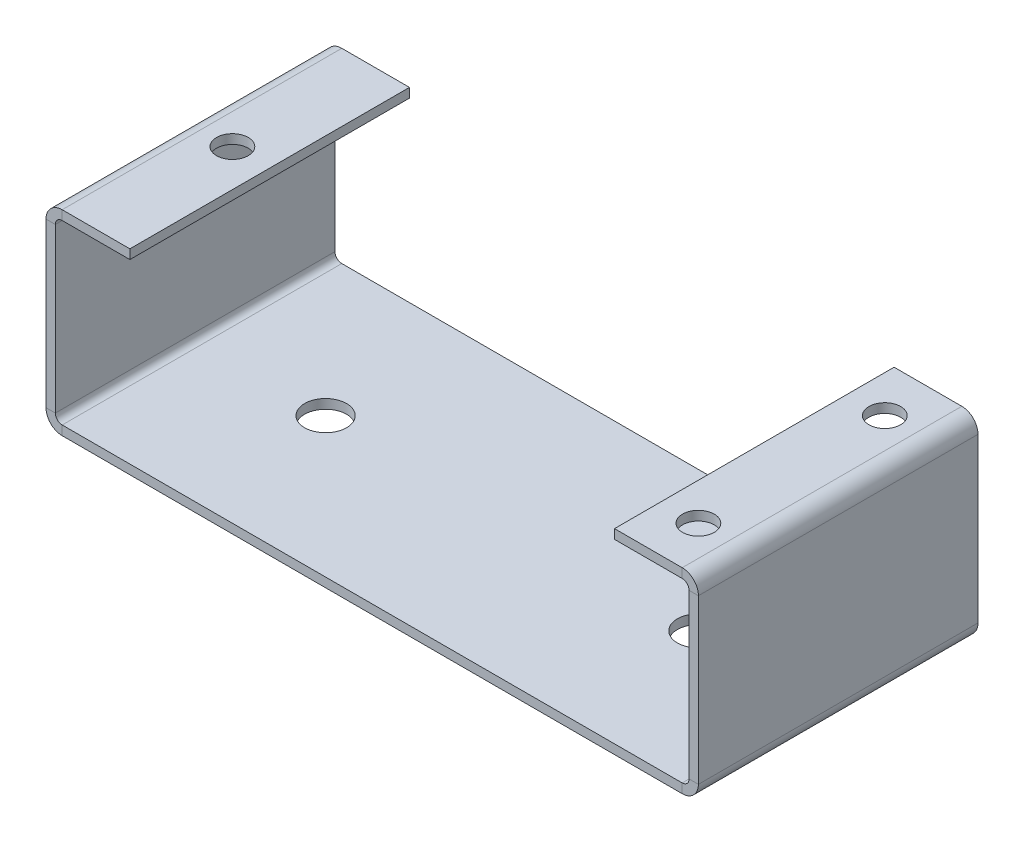
SolidWorks part; units mm, degrees
note: The reader was unsure of these and kept them because the rebuilt part matched: flange length of "Tôle pliée sur arête1", "Tôle pliée sur arête2".
ref_plane "Plan de face" through (0, 0, 0) normal (0, 0, 1) x (1, 0, 0)
ref_plane "Plan de dessus" through (0, 0, 0) normal (0, 1, 0) x (1, 0, 0)
ref_plane "Plan de droite" through (0, 0, 0) normal (1, 0, 0) x (0, 0, -1)
sketch "Esquisse1" plane through (0, 0, 0) normal (0, 1, 0) x (1, 0, 0)
  line L1 (-35, -15) -> (35, -15)
  line L2 (-35, -15) -> (-35, 15)
  line L3 (-35, 15) -> (35, 15)
  line L4 (35, -15) -> (35, 15)
  line L5 (-35, -15) -> (35, 15) construction
  line L6 (-35, 15) -> (35, -15) construction
  line L9 (-11.55, 0) -> (11.55, 0) construction
  point P0 (0, 0)
  dimension "D1" = 30
  dimension "D2" = 70
base flange "Tôle de base pliée1" sketch "Esquisse1" thickness 1 reverse thickness direction yes parameters "D1"=0.7366
edge flange "Tôle pliée sur arête1" sketch "Esquisse8" flange profiles "Esquisse8", "Esquisse36" flange angle 90 flange length 20 flange position material inside bend radius 0.7366 thickness 1 relief rectangular parameters "D6"=10, "D8"=1
sketch "Esquisse8" plane through (-35, 1, 0) normal (-1, 0, 0) x (0, 0, 1)
  line L0 (-15, 0) -> (15, 0) construction
  line L1 (-15, 0) -> (15, 0)
  line L2 (-15, 0) -> (-15, 20)
  line L3 (-15, 20) -> (15, 20)
  line L4 (15, 20) -> (15, 0)
sketch "Esquisse36" plane through (35, 1, 0) normal (1, 0, 0) x (0, 0, -1)
  line L0 (-15, 0) -> (15, 0) construction
  line L1 (-15, 0) -> (15, 0)
  line L2 (-15, 0) -> (-15, 20)
  line L3 (-15, 20) -> (15, 20)
  line L4 (15, 20) -> (15, 0)
bend "Pli d'arête1" bend radius 0.7366 bend angle 90 parameters "D5"=1
bend "Pli d'arête5" bend radius 0.7366 bend angle 90 parameters "D5"=3
edge flange "Tôle pliée sur arête2" sketch "Esquisse11" flange profiles "Esquisse11", "Esquisse38" flange angle 90 flange length 9 flange position material inside bend radius 0.7366 thickness 1 relief rectangular parameters "D6"=10, "D8"=1
sketch "Esquisse11" plane through (-34, 21, 0) normal (0, 1, 0) x (0, 0, 1)
  line L0 (15, 0) -> (-15, 0) construction
  line L1 (15, 0) -> (-15, 0)
  line L2 (-15, 0) -> (-15, 8)
  line L3 (-15, 8) -> (15, 8)
  line L4 (15, 8) -> (15, 0)
sketch "Esquisse38" plane through (34, 21, 0) normal (0, 1, 0) x (0, 0, -1)
  line L0 (15, 0) -> (-15, 0) construction
  line L1 (15, 0) -> (-15, 0)
  line L2 (-15, 0) -> (-15, 8)
  line L3 (-15, 8) -> (15, 8)
  line L4 (15, 8) -> (15, 0)
bend "Pli d'arête2" bend radius 0.7366 bend angle 90 parameters "D5"=2
bend "Pli d'arête6" bend radius 0.7366 bend angle 90 parameters "D5"=5
sketch "Esquisse12" plane through (0, 21, 0) normal (0, 1, 0) x (1, 0, 0)
  line L0 (-11.55, 0) -> (11.55, 0) construction
  line L2 (35, 15) -> (35, -15) construction
  line L3 (33.2634, 15) -> (26, 15) construction
  line L7 (-35, -15) -> (-35, 15) construction
  circle A2 centre (-30, 0) radius 1.7
  circle A3 centre (30, 10) radius 1.7
  circle A4 centre (30, -10) radius 1.7
  dimension "D2" = 5
  dimension "D3" = 3.4
  dimension "D1" = 3.4
  dimension "D4" = 5
  dimension "D5" = 5
extrude "Enlèv. mat.-Extru.1" cut sketch "Esquisse12" against normal up to next normal cut yes
sketch "Esquisse27" plane through (0, 1, 0) normal (0, 1, 0) x (1, 0, 0)
  line L0 (-11.55, 0) -> (11.55, 0) construction
  line L1 (0, -11.55) -> (0, 11.55) construction
  circle A0 centre (-20, 0) radius 2.25
  circle A1 centre (20, 0) radius 2.25
  dimension "D1" = 4.5
  dimension "D2" = 20
extrude "Enlèv. mat.-Extru.3" cut sketch "Esquisse27" against normal up to next normal cut yes
sketch "Lignes de pliage1" [suppressed] plane through (0, 0, 0) normal (0, 1, 0) x (1, 0, 0)
sketch "Cube de visualisation1" [suppressed] plane through (0, 0, 0) normal (0, 1, 0) x (1, 0, 0)
sheet metal parameters "Tôlerie1" thickness 1 parameters "D1"=0.7366
flat pattern "Etat déplié1" [suppressed]
sketch "Lignes de pliage2" plane through (0, 0, 0) normal (0, 1, 0) x (1, 0, 0)
sketch3d "Cube de visualisation2" [suppressed]
  line L0 (26.75, 15, 0) -> (-26.75, 15, 0) construction
  line L1 (26.75, -15, 0) -> (-26.75, -15, 0) construction
  line L2 (26.75, 15, 0) -> (26.75, -15, 0) construction
  line L3 (-26.75, 15, 0) -> (-26.75, -15, 0) construction
sheet metal parameters "Tôlerie2" thickness 1 parameters "D1"=0.7366
flat pattern "Etat déplié1" [suppressed]
sketch "Lignes de pliage2" plane through (0, 0, 0) normal (0, -1, 0) x (-1, 0, 0)
  line L0 (26.9846, -15) -> (26.9846, 15) construction
  line L1 (26.9846, -15) -> (26.9846, 15) construction
sketch3d "Cube de visualisation2" [suppressed]
  line L0 (-26.75, 15, 0) -> (46.2192, 15, 0) construction
  line L1 (-26.75, -15, 0) -> (46.2192, -15, 0) construction
  line L2 (-26.75, 15, 0) -> (-26.75, -15, 0) construction
  line L3 (46.2192, 15, 0) -> (46.2192, -15, 0) construction
bend of the flat pattern "Dépliage-<Pli d'arête1>1"
bend of the flat pattern "Dépliage-<Pli d'arête5>1"
sheet metal parameters "Tôlerie3" thickness 1 parameters "D1"=0.7366
flat pattern "Etat déplié1" [suppressed]
sketch "Lignes de pliage2" plane through (0, 0, 0) normal (0, -1, 0) x (-1, 0, 0)
  line L0 (26.9846, -15) -> (26.9846, 15) construction
  line L1 (26.9846, -15) -> (26.9846, 15) construction
  line L2 (45.4539, -15) -> (45.4539, 15) construction
  line L3 (45.4539, -15) -> (45.4539, 15) construction
sketch3d "Cube de visualisation2" [suppressed]
  line L0 (-26.75, 15, 0) -> (51.6885, 15, 0) construction
  line L1 (-26.75, -15, 0) -> (51.6885, -15, 0) construction
  line L2 (-26.75, 15, 0) -> (-26.75, -15, 0) construction
  line L3 (51.6885, 15, 0) -> (51.6885, -15, 0) construction
bend of the flat pattern "Dépliage-<Pli d'arête1>1"
bend of the flat pattern "Dépliage-<Pli d'arête2>1"
bend of the flat pattern "Dépliage-<Pli d'arête5>4"
bend of the flat pattern "Dépliage-<Pli d'arête6>1"
sheet metal parameters "Tôlerie4" thickness 1 parameters "D1"=0.7366
flat pattern "Etat déplié1" [suppressed]
sketch "Lignes de pliage2" plane through (0, 0, 0) normal (0, -1, 0) x (-1, 0, 0)
  line L0 (26.9846, -15) -> (26.9846, 15) construction
  line L1 (26.9846, -15) -> (26.9846, 15) construction
  line L2 (45.4539, -15) -> (45.4539, 15) construction
  line L3 (45.4539, -15) -> (45.4539, 15) construction
sketch3d "Cube de visualisation2" [suppressed]
  line L0 (-26.75, -16.5, 0) -> (51.6885, -16.5, 0) construction
  line L1 (-26.75, 16.5, 0) -> (51.6885, 16.5, 0) construction
  line L2 (-26.75, -16.5, 0) -> (-26.75, 16.5, 0) construction
  line L3 (51.6885, -16.5, 0) -> (51.6885, 16.5, 0) construction
bend of the flat pattern "Dépliage-<Pli d'arête1>1"
bend of the flat pattern "Dépliage-<Pli d'arête5>2"
bend of the flat pattern "Dépliage-<Pli d'arête2>1"
bend of the flat pattern "Dépliage-<Pli d'arête6>2"
sheet metal parameters "Tôlerie8" thickness 1 parameters "D1"=0.7366
flat pattern "Etat déplié1"
sketch "Lignes de pliage2" plane through (0, 0, 0) normal (0, -1, 0) x (-1, 0, 0)
  line L0 (34.2346, -15) -> (34.2346, 15) construction
  line L1 (34.2346, -15) -> (34.2346, 15) construction
  line L2 (-53.7039, 15) -> (-53.7039, -15) construction
  line L3 (53.7039, -15) -> (53.7039, 15) construction
  line L4 (-53.7039, 15) -> (-53.7039, -15) construction
  line L5 (53.7039, -15) -> (53.7039, 15) construction
  line L8 (-34.2346, 15) -> (-34.2346, -15) construction
  line L9 (-34.2346, 15) -> (-34.2346, -15) construction
sketch3d "Cube de visualisation2" [suppressed]
  line L0 (-61.9385, 15, 0) -> (61.9385, 15, 0) construction
  line L1 (-61.9385, -15, 0) -> (61.9385, -15, 0) construction
  line L2 (-61.9385, 15, 0) -> (-61.9385, -15, 0) construction
  line L3 (61.9385, 15, 0) -> (61.9385, -15, 0) construction
bend of the flat pattern "Dépliage-<Pli d'arête1>1"
bend of the flat pattern "Dépliage-<Pli d'arête5>3"
bend of the flat pattern "Dépliage-<Pli d'arête2>1"
bend of the flat pattern "Dépliage-<Pli d'arête6>3"
